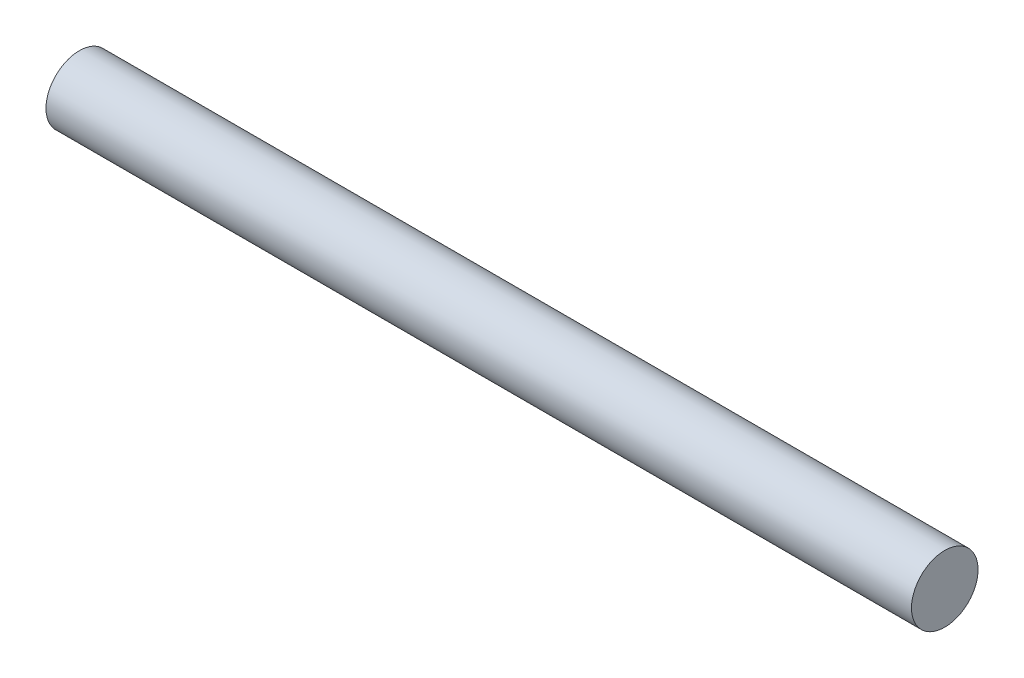
SolidWorks part; units mm, degrees
ref_plane "正面" through (0, 0, 0) normal (0, 0, 1) x (1, 0, 0)
ref_plane "平面" through (0, 0, 0) normal (0, 1, 0) x (1, 0, 0)
ref_plane "右側面" through (0, 0, 0) normal (1, 0, 0) x (0, 0, -1)
sketch "ｽｹｯﾁ1" plane through (0, 0, 0) normal (0, 0, 1) x (1, 0, 0)
  line L0 (0, 0) -> (39, 0) construction
  line L1 (0, 0) -> (0, 3)
  line L2 (0, 3) -> (35, 3)
  line L3 (35, 3) -> (35, 2) construction
  line L4 (35, 2) -> (36, 2) construction
  line L5 (36, 2) -> (36, 3) construction
  line L6 (36, 3) -> (39, 3)
  line L7 (39, 3) -> (39, 0)
  line L8 (0, 0) -> (39, 0)
  line L9 (35, 3) -> (36, 3)
  dimension "D1" = 1
  dimension "D2" = 3
  dimension "D3" = 3
  dimension "D4" = 35
revolve "回転1" add sketch "ｽｹｯﾁ1" angle 360 about L0
mirror "ﾐﾗｰ1" about plane through (0, 0, 0) normal (1, 0, 0) of bodies 105
